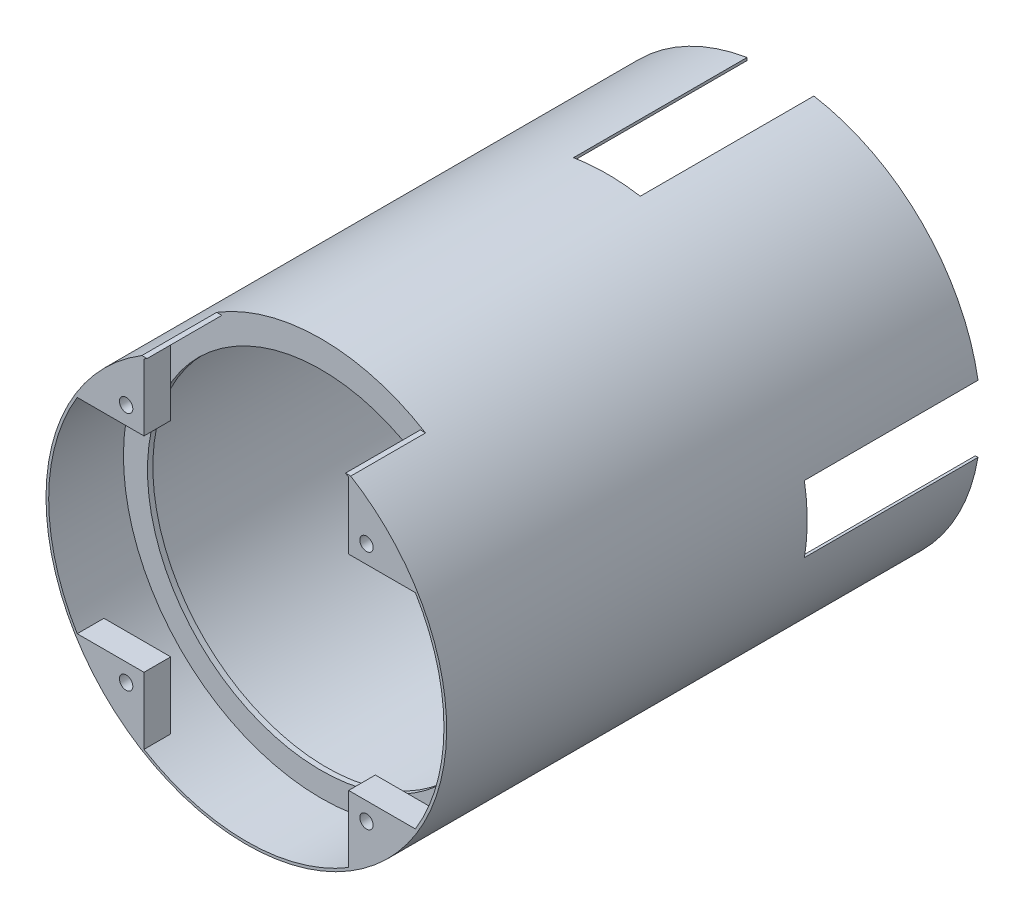
SolidWorks part; units mm, degrees
material "ABS"
ref_plane "前视基准面" through (0, 0, 0) normal (0, 0, 1) x (1, 0, 0)
ref_plane "上视基准面" through (0, 0, 0) normal (0, 1, 0) x (1, 0, 0)
ref_plane "右视基准面" through (0, 0, 0) normal (1, 0, 0) x (0, 0, -1)
sketch "草图1" plane through (0, 0, 0) normal (0, 0, 1) x (1, 0, 0)
  circle A0 centre (0, 0) radius 75
  dimension "D1" = 150
extrude "凸台-拉伸1" add sketch "草图1" along normal blind 100 and the other way blind 100
shell "抽壳1" thickness 1 removed face at (75, 0, -100) removed face at (75, 0, 100)
ref_plane "基准面1" through (0, 0, 70) normal (0, 0, 1) x (1, 0, 0)
sketch "草图2" plane through (0, 0, 70) normal (0, 0, 1) x (1, 0, 0)
  circle A0 centre (0, 0) radius 75
  circle A1 centre (0, 0) radius 65
  dimension "D1" = 150
  dimension "D2" = 130
extrude "凸台-拉伸2" add sketch "草图2" along normal blind 2
sketch "草图3" plane through (0, 0, 100) normal (0, 0, 1) x (1, 0, 0)
  line L0 (0, 0) -> (0, 116.4423) construction
  line L1 (39.1024, 64) -> (-39.1024, 64)
  circle A0 centre (0, 0) radius 75 construction
  arc A1 (39.1024, 64) -> (-39.1024, 64) centre (0, 0) ccw
  point P10 (0, 64)
extrude "切除-拉伸1" cut sketch "草图3" against normal up to surface (28 mm away) up to face at (65, 0, 72)
sketch "草图5" plane through (0, 0, 0) normal (0, 1, 0) x (1, 0, 0)
  line L0 (0, 0) -> (0, 70) construction
  line L1 (12.5, 35) -> (-12.5, 35)
  line L2 (12.5, 35) -> (12.5, 105)
  line L3 (12.5, 105) -> (-12.5, 105)
  line L4 (-12.5, 35) -> (-12.5, 105)
  line L5 (12.5, 35) -> (-12.5, 105) construction
  line L6 (12.5, 105) -> (-12.5, 35) construction
  point P0 (0, 70)
  dimension "D1" = 70
  dimension "D2" = 35
  dimension "D3" = 25
extrude "切除-拉伸2" cut sketch "草图5" against normal through all and the other way through all
pattern_circular "阵列(圆周)1" count 4 over 360 about axis through (0, 0, -100) along (0, 0, 1) of "切除-拉伸2"
sketch "草图6" plane through (0, 0, 100) normal (0, 0, 1) x (1, 0, 0)
  line L0 (0, 0) -> (-108.246, 0) construction
  line L1 (0, 0) -> (0, 124.1185) construction
  line L4 (0, 0) -> (-38.3109, 38.3109) construction
  line L6 (-38.3109, 38.3109) -> (-38.3109, 63.3109)
  line L7 (-63.3109, 38.3109) -> (-38.3109, 38.3109)
  arc A0 (-37.1484, 64) -> (37.1484, 64) centre (0, 0) ccw construction
  arc A1 (-63.3109, 38.3109) -> (-38.3109, 63.3109) centre (0, 0) cw
  circle A2 centre (-45, 45) radius 2.5
  dimension "D2" = 5
  dimension "D3" = 45
  dimension "D1" = 25
  dimension "D4" = 45
extrude "凸台-拉伸3" add sketch "草图6" against normal blind 10
pattern_circular "阵列(圆周)2" count 4 over 360 about axis through (0, 0, 100) along (0, 0, 1) of "凸台-拉伸3"
